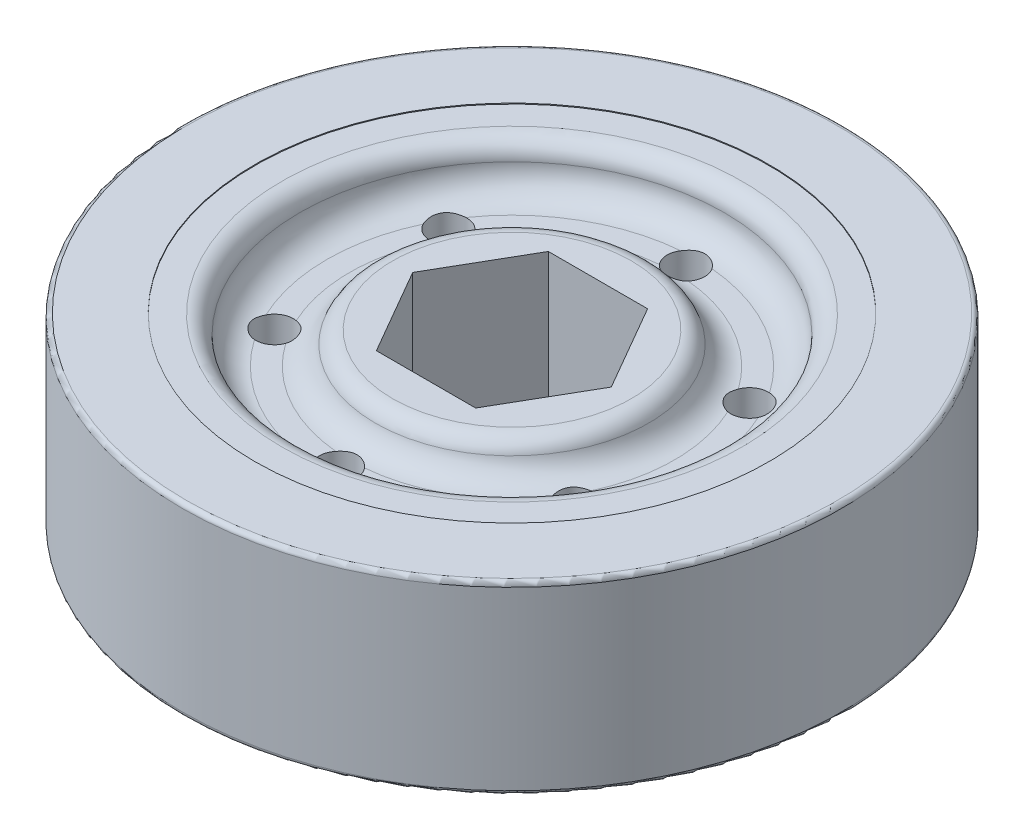
SolidWorks part; units mm, degrees
ref_plane "Front Plane" through (0, 0, 0) normal (0, 0, 1) x (1, 0, 0)
ref_plane "Top Plane" through (0, 0, 0) normal (0, 1, 0) x (1, 0, 0)
ref_plane "Right Plane" through (0, 0, 0) normal (1, 0, 0) x (0, 0, -1)
sketch "Sketch1" plane through (0, 0, 0) normal (0, 1, 0) x (1, 0, 0)
  line L1 (10.9985, 0) -> (5.4993, 9.525)
  line L2 (5.4993, 9.525) -> (-5.4993, 9.525)
  line L3 (-5.4993, 9.525) -> (-10.9985, 0)
  line L4 (-10.9985, 0) -> (-5.4993, -9.525)
  line L5 (-5.4993, -9.525) -> (5.4993, -9.525)
  line L6 (5.4993, -9.525) -> (10.9985, 0)
  circle A0 centre (0, 0) radius 28.5
  circle A1 centre (0, 0) radius 23.5
  circle A2 centre (0, 0) radius 15
  circle A3 centre (0, 0) radius 9.525 construction
  circle A4 centre (0, 0) radius 36.5125
  dimension "D1" = 57
  dimension "D2" = 5
extrude "Boss-Extrude1" add sketch "Sketch1" along normal blind 10.16 and the other way blind 10.16 contours A0 A1 region at (-27.6939, 0, 0)
extrude "Boss-Extrude2" add sketch "Sketch1<3>" along normal blind 5.16 and the other way blind 5.16 contours A1 A2 region at (-22.8353, 0, 0)
sketch "Sketch1<3>" plane through (0, 0, 0) normal (0, 1, 0) x (1, 0, 0) same geometry as "Sketch1"
extrude "Boss-Extrude3" add sketch "Sketch1<4>" along normal blind 8.66 and the other way blind 8.66 contours A2 L6 L5 L4 L3 L2 L1 region at (-14.5757, 0, 0)
sketch "Sketch1<4>" plane through (0, 0, 0) normal (0, 1, 0) x (1, 0, 0) same geometry as "Sketch1"
extrude "Boss-Extrude4" add sketch "Sketch1<5>" along normal blind 10.26 and the other way blind 10.26 contours A4 A0 region at (-35.4798, 0, 0)
sketch "Sketch1<5>" plane through (0, 0, 0) normal (0, 1, 0) x (1, 0, 0) same geometry as "Sketch1"
fillet "Fillet1" radius 3 2 edges at (0, 5.16, 23.5) (0, 5.16, 15)
fillet "Fillet2" radius 2 2 edges at (0, 8.66, 15) (0, 10.16, 23.5)
fillet "Fillet3" radius 3 2 edges at (0, -5.16, 15) (0, -5.16, 23.5)
fillet "Fillet4" radius 2 2 edges at (0, -10.16, 23.5) (0, -8.66, 15)
fillet "Fillet5" radius 0.5 2 edges at (0, -10.26, 36.5125) (0, 10.26, 36.5125)
sketch "Sketch2" plane through (0, 5.16, 0) normal (0, 1, 0) x (1, 0, 0)
  circle A0 centre (0, 19.2689) radius 2.0828
  circle A1 centre (16.6874, 9.6345) radius 2.0828
  circle A2 centre (16.6874, -9.6345) radius 2.0828
  circle A3 centre (0, -19.2689) radius 2.0828
  circle A4 centre (-16.6874, -9.6345) radius 2.0828
  circle A5 centre (-16.6874, 9.6345) radius 2.0828
  point P14 (0, 0)
  dimension "D1" = 6
extrude "Cut-Extrude1" cut sketch "Sketch2" against normal through all and the other way blind 10.16
